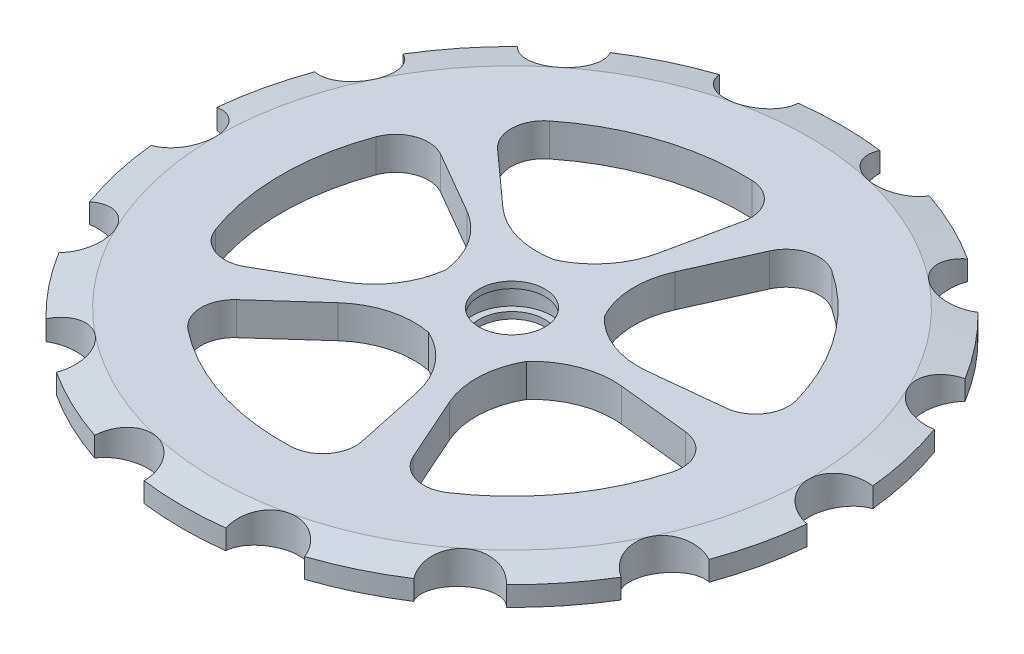
SolidWorks part; units mm, degrees
ref_plane "Спереди" through (0, 0, 0) normal (0, 0, 1) x (1, 0, 0)
ref_plane "Сверху" through (0, 0, 0) normal (0, 1, 0) x (1, 0, 0)
ref_plane "Справа" through (0, 0, 0) normal (1, 0, 0) x (0, 0, -1)
sketch "Эскиз1" plane through (0, 0, 0) normal (0, 0, 1) x (1, 0, 0)
  line L0 (0, 0) -> (0, 36.4583) construction
  line L1 (0, 0) -> (0, 10)
  line L2 (0, 10) -> (90, 10)
  line L3 (90, 10) -> (100, 8)
  line L4 (0, 5) -> (107.3663, 5) construction
  line L5 (100, 8) -> (100, 2)
  line L6 (90, 0) -> (100, 2)
  line L7 (0, 0) -> (90, 0)
  point P8 (90.3373, 10)
  point P11 (100, 5)
  dimension "D1" = 10
  dimension "D2" = 100
  dimension "D3" = 90
  dimension "D4" = 3
revolve "Повернуть1" add sketch "Эскиз1" angle 360 about L0
sketch "Эскиз3" plane through (0, 0, 0) normal (0, 0, 1) x (1, 0, 0)
  line L0 (0, 0) -> (0, 19.0373) construction
  line L1 (-10, 8) -> (-12, 8)
  line L2 (0, 0) -> (-10, 0)
  line L3 (0, 0) -> (0, 10)
  line L4 (0, 10) -> (-10, 10)
  line L5 (-10, 0) -> (-10, 2)
  line L6 (-12, 8) -> (-12, 2)
  line L11 (90, 10) -> (-90, 10) construction
  line L12 (-90, 0) -> (90, 0) construction
  line L13 (100, 2) -> (-100, 2) construction
  line L14 (100, 8) -> (-100, 8) construction
  line L15 (-10, 2) -> (-12, 2)
  line L16 (-10, 8) -> (-10, 10)
  point P7 (0, 0)
  point P8 (0, 0)
  point P9 (0, 0)
  point P10 (-14.343, 5.0571)
  point P11 (0, 0)
  point P14 (0, 0)
  point P24 (-12, 5)
  point P25 (0, 0)
  point P26 (0, 0)
  dimension "D2" = 2
  dimension "D1" = 10
revolve "Вырез-Повернуть1" cut sketch "Эскиз3" angle 360 about L0
sketch "Эскиз4" plane through (0, 0, 0) normal (0, 0, 1) x (1, 0, 0)
  line L0 (-100, 0) -> (-100, 17.5763) construction
  line L2 (-100, 0) -> (-90, 0)
  line L3 (-100, 0) -> (-100, 10)
  line L4 (-100, 10) -> (-90, 10)
  line L5 (-90, 0) -> (-90, 10)
  line L6 (10, 10) -> (-10, 10) construction
  line L7 (-10, 0) -> (10, 0) construction
  point P6 (0, 0)
  point P7 (0, 0)
  point P8 (0, 0)
  point P9 (0, 0)
  point P12 (0, 0)
  point P15 (0, 0)
  point P16 (-100, 0)
  dimension "D1" = 20
  dimension "D2" = 100
revolve "Вырез-Повернуть2" cut sketch "Эскиз4" angle 360 about L0
pattern_circular "Круговой массив1" count 14 over 360 about axis through (0, 10, 0) along (0, -1, 0) of "Вырез-Повернуть2"
sketch "Эскиз5" plane through (0, 0, 0) normal (0, 0, 1) x (1, 0, 0)
  line L0 (0, 0) -> (0, 17.8942) construction
  line L1 (-20.0269, 10) -> (-56.1141, 10) construction
  line L2 (-70, 10) -> (-20, 10)
  line L3 (-70, 10) -> (-70, 0)
  line L4 (-70, 0) -> (-20, 0)
  line L5 (-20, 10) -> (-20, 0)
  line L6 (-20.0269, 0) -> (20.0269, 0) construction
  dimension "D1" = 140
  dimension "D2" = 40
revolve "Вырез-Повернуть3" cut sketch "Эскиз5" angle 60 mid plane about L0
fillet "Скругление2" radius 25 2 edges at (-17.3205, 5, -10) (-17.3205, 5, 10)
fillet "Скругление3" radius 10 2 edges at (-60.6218, 5, -35) (-60.6218, 5, 35)
pattern_circular "Круговой массив3" count 5 over 360 about axis through (0, 10, 0) along (0, -1, 0) of "Вырез-Повернуть3", "Скругление2", "Скругление3"
